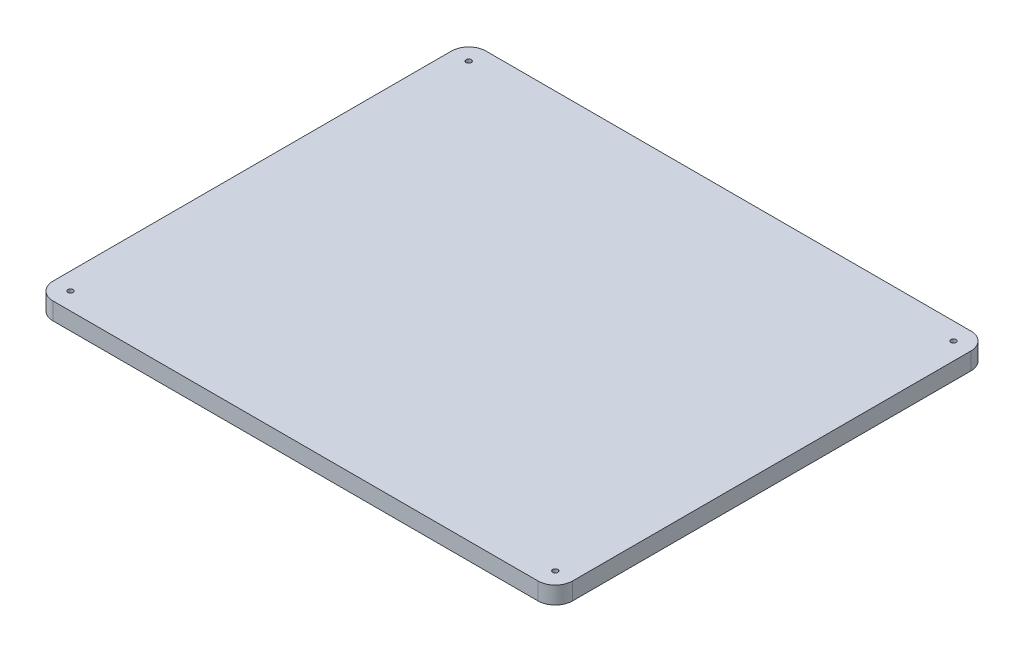
SolidWorks part; units mm, degrees
ref_plane "Спереди" through (0, 0, 0) normal (0, 0, 1) x (1, 0, 0)
ref_plane "Сверху" through (0, 0, 0) normal (0, 1, 0) x (1, 0, 0)
ref_plane "Справа" through (0, 0, 0) normal (1, 0, 0) x (0, 0, -1)
sketch "Эскиз1" plane through (0, 0, 0) normal (0, 1, 0) x (1, 0, 0)
  line L1 (150, -125) -> (-150, -125)
  line L2 (150, -125) -> (150, 125)
  line L3 (150, 125) -> (-150, 125)
  line L4 (-150, -125) -> (-150, 125)
  line L5 (150, -125) -> (-150, 125) construction
  line L6 (150, 125) -> (-150, -125) construction
  point P0 (0, 0)
  dimension "D1" = 250
  dimension "D2" = 300
extrude "Бобышка-Вытянуть1" add sketch "Эскиз1" along normal mid plane 10
fillet "Скругление1" radius 10 4 edges at (-150, 0, -125) (150, 0, -125) (150, 0, 125) (-150, 0, 125)
sketch "Эскиз2" plane through (0, 5, 0) normal (0, 1, 0) x (1, 0, 0)
  line L0 (0, 0) -> (0, -33.246) construction
  line L1 (0, 0) -> (-47.6996, 0) construction
  circle A0 centre (-140, 115) radius 1.5
  circle A1 centre (-140, -115) radius 1.5
  circle A2 centre (140, -115) radius 1.5
  circle A3 centre (140, 115) radius 1.5
extrude "Вырез-Вытянуть1" cut sketch "Эскиз2" against normal up to surface (10 mm away) up to face at (0, -5, 0)
